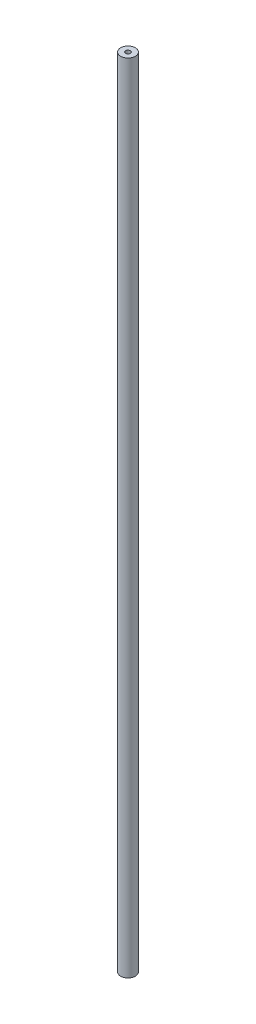
SolidWorks part; units mm, degrees
material "6061-T6 (SS)"
ref_plane "Front Plane" through (0, 0, 0) normal (0, 0, 1) x (1, 0, 0)
ref_plane "Top Plane" through (0, 0, 0) normal (0, 1, 0) x (1, 0, 0)
ref_plane "Right Plane" through (0, 0, 0) normal (1, 0, 0) x (0, 0, -1)
sketch "Sketch1" plane through (0, 0, 0) normal (0, 1, 0) x (1, 0, 0)
  circle A0 centre (0, 0) radius 6.35
  dimension "D1" = 12.7
extrude "Boss-Extrude1" add sketch "Sketch1" along normal blind 685.8
hole_wizard "#10-32 Tapped Hole1" positions "Sketch2" profile "Sketch4" tap size "#10-32" standard "ANSI Inch"
sketch "Sketch2" plane through (0, 0, 0) normal (0, -1, 0) x (-1, 0, 0)
  point P0 (0, 0)
sketch "Sketch4" plane through (0, 0, 0) normal (1, 0, 0) x (0, 0, -1)
  line L0 (0, 0) -> (0, 13.2428)
  line L1 (0, 13.2428) -> (2.0193, 12.0294)
  line L2 (2.0193, 12.0294) -> (2.0193, 0)
  line L5 (2.0193, 0) -> (0, 0)
  line L10 (0, 13.2428) -> (-2.0193, 12.0294) construction
  line L11 (0, -6.35) -> (0, 107.95) construction
  dimension "Tap Drill Dia." = 4.0386
  dimension "Tap Drill Depth" = 12.0294
  dimension "Drill Angle" = 118
cosmetic thread "Hole Thread1"
hole_wizard "#10-32 Tapped Hole2" positions "Sketch5" profile "Sketch6" tap size "#10-32" standard "ANSI Inch"
sketch "Sketch5" plane through (0, 685.8, 0) normal (0, 1, 0) x (1, 0, 0)
  point P0 (0, 0)
sketch "Sketch6" plane through (0, 685.8, 0) normal (1, 0, 0) x (0, 0, 1)
  line L0 (0, 0) -> (0, 13.2428)
  line L1 (0, 13.2428) -> (2.0193, 12.0294)
  line L2 (2.0193, 12.0294) -> (2.0193, 0)
  line L5 (2.0193, 0) -> (0, 0)
  line L10 (0, 13.2428) -> (-2.0193, 12.0294) construction
  line L11 (0, -6.35) -> (0, 107.95) construction
  dimension "Tap Drill Dia." = 4.0386
  dimension "Tap Drill Depth" = 12.0294
  dimension "Drill Angle" = 118
cosmetic thread "Hole Thread2"
